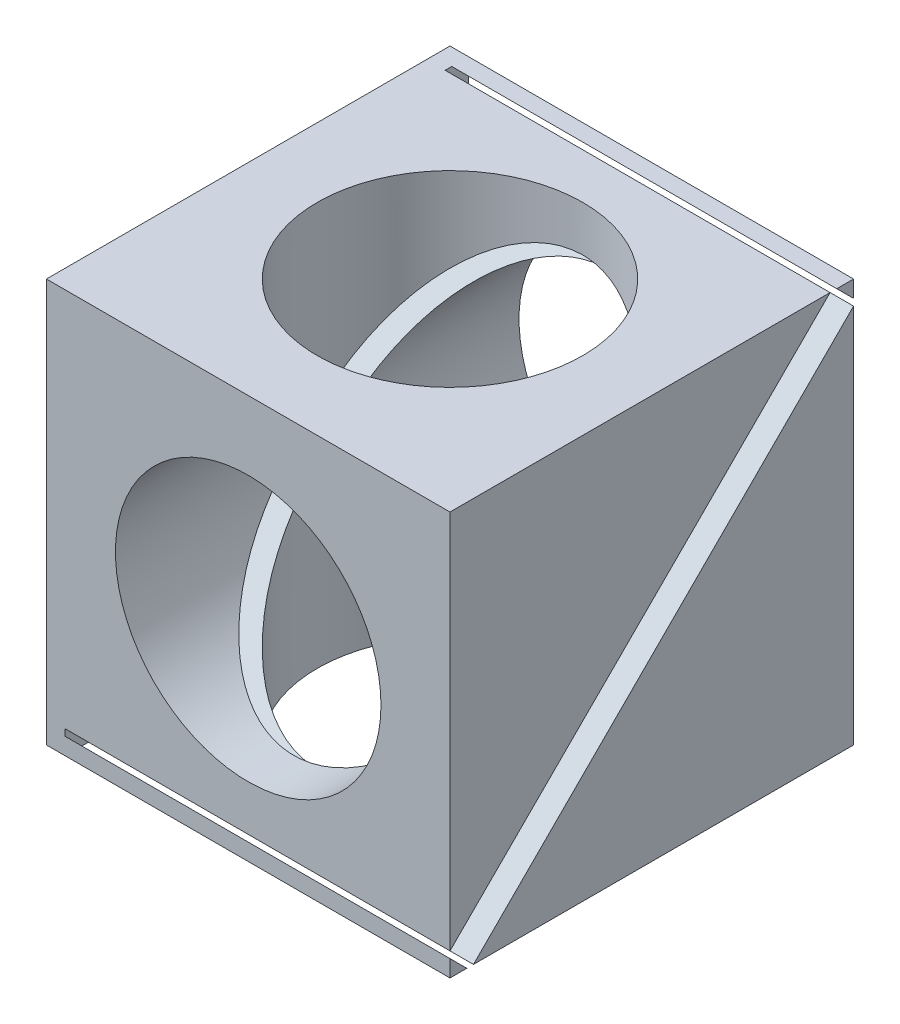
SolidWorks part; units mm, degrees
ref_plane "Front Plane" through (0, 0, 0) normal (0, 0, 1) x (1, 0, 0)
ref_plane "Top Plane" through (0, 0, 0) normal (0, 1, 0) x (1, 0, 0)
ref_plane "Right Plane" through (0, 0, 0) normal (1, 0, 0) x (0, 0, -1)
sketch "Sketch1" plane through (0, 0, 0) normal (0, 1, 0) x (1, 0, 0)
  line L1 (-19.304, -19.304) -> (19.304, -19.304)
  line L2 (-19.304, -19.304) -> (-19.304, 19.304)
  line L3 (-19.304, 19.304) -> (19.304, 19.304)
  line L4 (19.304, -19.304) -> (19.304, 19.304)
  line L5 (-19.304, -19.304) -> (19.304, 19.304) construction
  line L6 (-19.304, 19.304) -> (19.304, -19.304) construction
  point P0 (0, 0)
  dimension "D1" = 38.608
  dimension "D2" = 38.608
extrude "Boss-Extrude1" add sketch "Sketch1" along normal mid plane 38.608
sketch "Sketch2" plane through (0, 0, 0) normal (0, 0, 1) x (1, 0, 0)
  circle A0 centre (0, 0) radius 12.7
  dimension "D1" = 25.4
extrude "Cut-Extrude1" cut sketch "Sketch2" against normal through all both and the other way through all
sketch "Sketch3" plane through (0, 19.304, 0) normal (0, -1, 0) x (0, 0, -1)
  circle A0 centre (0, 0) radius 12.7
  dimension "D1" = 25.4
extrude "Cut-Extrude3" cut sketch "Sketch3" against normal through all and the other way through all
sketch "Sketch4" plane through (0, 0, 0) normal (1, 0, 0) x (0, 0, -1)
  line L0 (-19.304, -19.304) -> (19.304, 19.304) construction
  line L1 (-17.3768, -19.6219) -> (19.6219, 17.3768)
  line L2 (-17.3768, -19.6219) -> (-19.6219, -17.3768)
  line L3 (-19.6219, -17.3768) -> (17.3768, 19.6219)
  line L4 (19.6219, 17.3768) -> (17.3768, 19.6219)
  line L5 (-17.3768, -19.6219) -> (17.3768, 19.6219) construction
  line L6 (-19.6219, -17.3768) -> (19.6219, 17.3768) construction
  line L7 (19.304, 19.304) -> (19.304, -19.304) construction
  point P0 (0, 0)
  point P11 (0, 0)
  point P12 (-18.4993, -18.4993)
  point P13 (0, 0)
  dimension "D1" = 3.175
  dimension "D2" = 52.324
extrude "Cut-Extrude4" cut sketch "Sketch4" against normal mid plane 35.052
extrude "Cut-Extrude5" cut sketch "Sketch4<2>" along normal through all
sketch "Sketch4<2>" plane through (0, 0, 0) normal (1, 0, 0) x (0, 0, -1) same geometry as "Sketch4"
